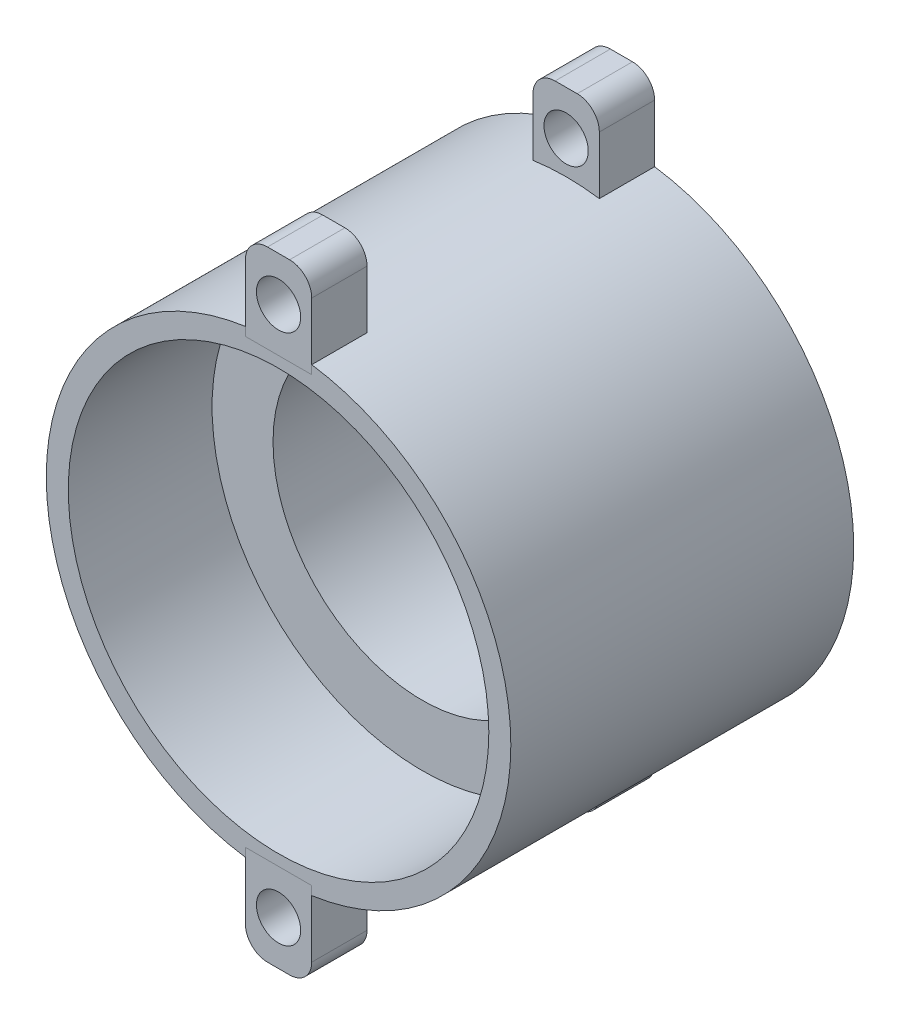
SolidWorks part; units mm, degrees
ref_plane "Front Plane" through (0, 0, 0) normal (0, 0, 1) x (1, 0, 0)
ref_plane "Top Plane" through (0, 0, 0) normal (0, 1, 0) x (1, 0, 0)
ref_plane "Right Plane" through (0, 0, 0) normal (1, 0, 0) x (0, 0, -1)
sketch "Sketch1" plane through (0, 0, 0) normal (0, 0, 1) x (1, 0, 0)
  circle A0 centre (0, 0) radius 13.5
  circle A1 centre (0, 0) radius 19.01
extrude "Boss-Extrude1" add sketch "Sketch1" along normal blind 18
sketch "Sketch2" plane through (0, 0, 18) normal (0, 0, 1) x (1, 0, 0)
  circle A0 centre (0, 0) radius 21
  circle A1 centre (0, 0) radius 19.01
extrude "Boss-Extrude2" add sketch "Sketch2" along normal blind 13 and the other way blind 18
sketch "Sketch3" plane through (0, 0, 0) normal (0, 0, -1) x (-1, 0, 0)
  line L0 (12.8914, 5.46) -> (17.4939, 7.4137)
  line L1 (15.5403, 12.0162) -> (10.9378, 10.0625)
  line L2 (15.5403, 12.0162) -> (19.4476, 2.8111)
  line L3 (19.4476, 2.8111) -> (14.8451, 0.8575)
  line L4 (10.9378, 10.0625) -> (14.8451, 0.8575)
  point P2 (12.8914, 5.46)
  point P6 (17.4939, 7.4137)
  dimension "D1" = 14
  dimension "D2" = 5.46
extrude "Cut-Extrude1" cut sketch "Sketch3" against normal offset from surface (13 mm away) 5 contours L1 L4 L3 L2 up to face at (19.01, 0, 18)
mirror "Mirror1" about plane through (0, 0, 0) normal (0, 1, 0) of "Cut-Extrude1"
mirror "Mirror2" about plane through (0, 0, 0) normal (1, 0, 0) of "Mirror1"
sketch "Sketch4" plane through (0, 0, 0) normal (0, 0, -1) x (-1, 0, 0)
  line L1 (-3, 28) -> (3, 28)
  line L2 (-3, 28) -> (-3, 20)
  line L3 (-3, 20) -> (3, 20)
  line L4 (3, 28) -> (3, 20)
  circle A0 centre (0, 24) radius 2
  point P4 (0, 20)
  dimension "D1" = 4
  dimension "D2" = 20
extrude "Boss-Extrude3" add sketch "Sketch4" along normal blind 0.0001 and the other way blind 5
fillet "Fillet1" radius 2 2 edges at (3, 28, 2.5) (-3, 28, 2.5)
mirror "Mirror5" about plane through (0, 0, 0) normal (0, 1, 0) of "Fillet1", "Boss-Extrude3"
sketch "Sketch7" plane through (0, 0, 31) normal (0, 0, 1) x (1, 0, 0)
  line L1 (-3, 28) -> (3, 28)
  line L2 (-3, 28) -> (-3, 20)
  line L3 (-3, 20) -> (3, 20)
  line L4 (3, 28) -> (3, 20)
  circle A0 centre (0, 24) radius 2
  point P4 (0, 20)
  dimension "D1" = 20
  dimension "D2" = 4
extrude "Boss-Extrude6" add sketch "Sketch7" along normal blind 0.0001 and the other way blind 5
mirror "Mirror6" about plane through (0, 0, 0) normal (0, 1, 0) of "Boss-Extrude6"
fillet "Fillet2" radius 2 4 edges at (-3, 28, 28.5) (3, 28, 28.5) (3, -28, 28.5) (-3, -28, 28.5)
